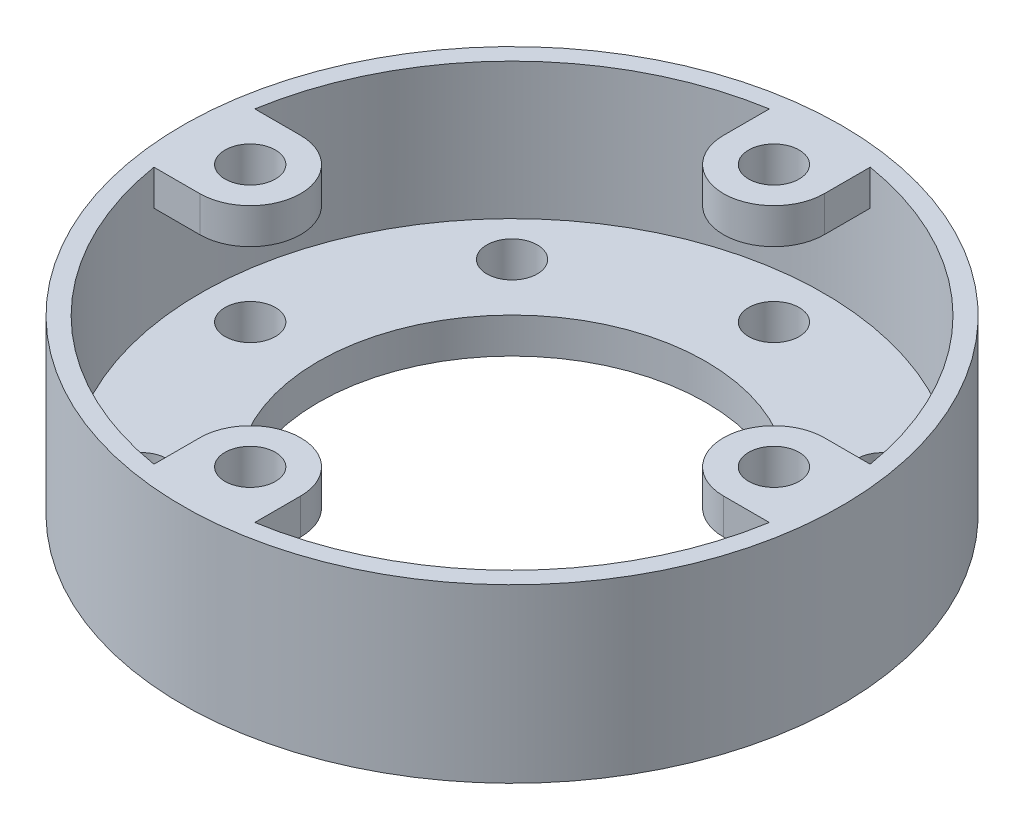
SolidWorks part; units mm, degrees
ref_plane "Front Plane" through (0, 0, 0) normal (0, 0, 1) x (1, 0, 0)
ref_plane "Top Plane" through (0, 0, 0) normal (0, 1, 0) x (1, 0, 0)
ref_plane "Right Plane" through (0, 0, 0) normal (1, 0, 0) x (0, 0, -1)
sketch "Sketch1" plane through (0, 0, 0) normal (0, 1, 0) x (1, 0, 0)
  circle A0 centre (0, 0) radius 73.025
  circle A1 centre (0, 0) radius 42.926
  dimension "D1" = 146.05
  dimension "D2" = 85.852
extrude "Boss-Extrude1" add sketch "Sketch1" along normal blind 38.1
sketch "Sketch2" plane through (0, 38.1, 0) normal (0, 1, 0) x (1, 0, 0)
  circle A0 centre (0, 0) radius 69.088
  dimension "D1" = 138.176
extrude "Cut-Extrude1" cut sketch "Sketch2" against normal blind 30.226
sketch "Sketch4" plane through (0, 38.1, 0) normal (0, 1, 0) x (1, 0, 0)
  line L0 (-68.1781, 11.176) -> (-58.0181, 11.176)
  line L1 (-11.175, 58.0191) -> (-11.175, 68.1791)
  line L2 (-58.0181, -11.176) -> (-68.1781, -11.176)
  line L3 (11.177, 68.1791) -> (11.177, 58.0191)
  line L4 (58.0201, 11.176) -> (68.1801, 11.176)
  line L5 (68.1801, -11.176) -> (58.0201, -11.176)
  line L6 (11.177, -58.0191) -> (11.177, -68.1791)
  line L7 (-11.175, -68.1791) -> (-11.175, -58.0191)
  circle A0 centre (0, 0) radius 69.088 construction
  arc A1 (-58.0181, 11.176) -> (-58.0181, -11.176) centre (-58.0181, 0) cw
  circle A2 centre (-58.0181, 0) radius 5.588
  circle A4 centre (0, 0) radius 58.0181 construction
  circle A5 centre (0.001, 0.001) radius 58.0181 construction
  arc A6 (11.177, 58.0191) -> (-11.175, 58.0191) centre (0.001, 58.0191) cw
  circle A7 centre (0.002, 0) radius 58.0181 construction
  arc A8 (58.0201, -11.176) -> (58.0201, 11.176) centre (58.0201, 0) cw
  circle A9 centre (0.001, -0.001) radius 58.0181 construction
  arc A10 (-11.175, -58.0191) -> (11.177, -58.0191) centre (0.001, -58.0191) cw
  circle A11 centre (0, 0) radius 58.0181 construction
  circle A12 centre (-41.025, 41.025) radius 5.588
  circle A13 centre (0, 0) radius 58.0181 construction
  circle A14 centre (0, 58.0181) radius 5.588
  circle A15 centre (0, 0) radius 58.0181 construction
  circle A16 centre (41.025, 41.025) radius 5.588
  circle A17 centre (0, 0) radius 58.0181 construction
  circle A18 centre (58.0181, 0) radius 5.588
  circle A19 centre (0, 0) radius 58.0181 construction
  circle A20 centre (41.025, -41.025) radius 5.588
  circle A21 centre (0, 0) radius 58.0181 construction
  circle A22 centre (0, -58.0181) radius 5.588
  circle A23 centre (0, 0) radius 58.0181 construction
  circle A24 centre (-41.025, -41.025) radius 5.588
  point P35 (0.001, 0)
  point P57 (0, 0)
  circle M3 centre (0, 0) radius 69.088
  dimension "D2" = 11.176
  dimension "D3" = 11.176
  dimension "D1" = 10.16
  dimension "D4" = 4
  dimension "D5" = 8
extrude "Boss-Extrude2" add sketch "Sketch4" against normal blind 7.874 contours A1 L0 L2 A2 M3 | A6 L3 L1 A14 M3 | A8 L5 L4 A18 M3 | A10 L7 L6 A22 M3 region at (-63.0981, 38.1, -10.8606) region at (0.001, 38.1, -68.7727) region at (-10.8597, 38.1, 63.0986) region at (68.5458, 38.1, -5.5809)
extrude "Cut-Extrude2" cut sketch "Sketch4<3>" against normal through all contours A12 | A16 | A20 | A24 region at (-41.025, 38.1, -41.025) region at (41.025, 38.1, -41.025) region at (41.025, 38.1, 41.025) region at (-41.025, 38.1, 41.025)
sketch "Sketch4<3>" plane through (0, 38.1, 0) normal (0, 1, 0) x (1, 0, 0) same geometry as "Sketch4"
extrude "Cut-Extrude3" cut sketch "Sketch4<4>" against normal through all contours A2 | A14 | A18 | A22 region at (-58.0181, 38.1, 0) region at (0, 38.1, -58.0181) region at (58.0181, 38.1, 0) region at (0, 38.1, 58.0181)
sketch "Sketch4<4>" plane through (0, 38.1, 0) normal (0, 1, 0) x (1, 0, 0) same geometry as "Sketch4"
